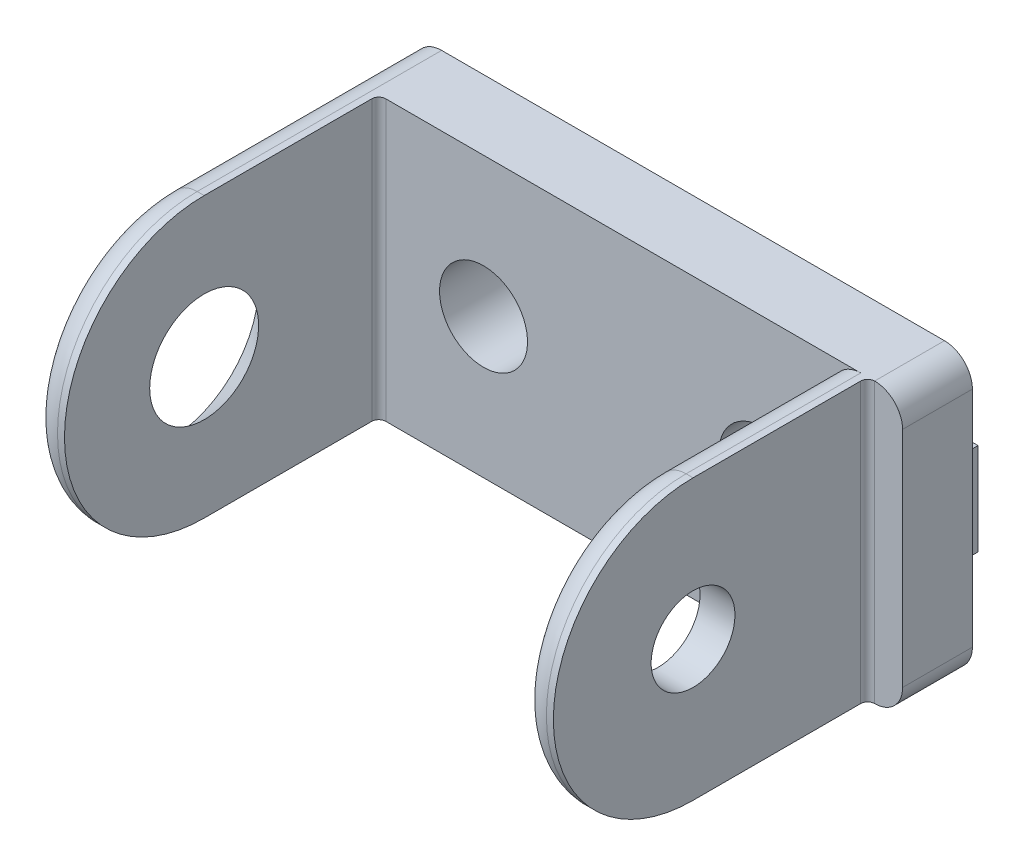
SolidWorks part; units mm, degrees
ref_plane "前视基准面" through (0, 0, 0) normal (0, 0, 1) x (1, 0, 0)
ref_plane "上视基准面" through (0, 0, 0) normal (0, 1, 0) x (1, 0, 0)
ref_plane "右视基准面" through (0, 0, 0) normal (1, 0, 0) x (0, 0, -1)
other "Configuration Table"
sketch "草图1" plane through (0, 0, 0) normal (0, 0, 1) x (1, 0, 0)
  line L0 (0, 0) -> (40, 0)
  line L1 (40, 0) -> (40, -20)
  line L2 (40, -20) -> (0, -20)
  line L3 (0, -20) -> (0, 0)
extrude "凸台-拉伸1" add sketch "草图1" along normal blind 5
sketch "草图2" plane through (0, 0, 0) normal (0, 0, 1) x (1, 0, 0)
  line L0 (0, 0) -> (2.5, 0)
  line L1 (2.5, 0) -> (2.5, -20)
  line L2 (0, -20) -> (40, -20) construction
  line L3 (2.5, -20) -> (0, -20)
  line L4 (0, -20) -> (0, 0)
  line L5 (0, 0) -> (0, -20)
extrude "凸台-拉伸2" add sketch "草图2" along normal blind 27.5 contours L4 L3 L1 L0 region at (1.25, -10, 0)
sketch "草图3" plane through (0, 0, 0) normal (0, 0, -1) x (-1, 0, 0)
  line L0 (0, -10) -> (-35.75, -10)
  line L1 (0, 0) -> (0, -20) construction
  line L2 (-40, -20) -> (-40, 0) construction
  line L3 (-35.75, -6.7) -> (-35.75, -13.3)
  line L4 (-35.75, -6.7) -> (-39, -6.7)
  line L5 (-39, -6.7) -> (-39, -13.3)
  line L6 (-39, -13.3) -> (-35.75, -13.3)
  line L7 (-39, -10) -> (-40, -10)
  line L20 (-33.3, -1) -> (-33.3, -4.25)
  line L21 (-26.7, -4.25) -> (-33.3, -4.25)
  line L22 (-26.7, -4.25) -> (-26.7, -1)
  line L23 (-26.7, -1) -> (-33.3, -1)
  line L24 (-35.75, -10) -> (-39, -10)
  line L25 (-20, -20) -> (-20, -10)
  line L26 (0, -20) -> (-40, -20) construction
  line L31 (-1, -6.7) -> (-1, -13.3)
  line L32 (-4.25, -6.7) -> (-1, -6.7)
  line L33 (-4.25, -6.7) -> (-4.25, -13.3)
  line L34 (-1, -13.3) -> (-4.25, -13.3)
  line L39 (-26.7, -19) -> (-26.7, -15.75)
  line L40 (-33.3, -15.75) -> (-26.7, -15.75)
  line L41 (-33.3, -15.75) -> (-33.3, -19)
  line L42 (-33.3, -19) -> (-26.7, -19)
  line L43 (-21, -6.7) -> (-24.25, -6.7) [skipped]
  line L44 (-21, -13.3) -> (-21, -6.7) [skipped]
  line L45 (-24.25, -13.3) -> (-21, -13.3) [skipped]
  line L46 (-24.25, -13.3) -> (-24.25, -6.7) [skipped]
  line L47 (-6.7208, -18.9792) -> (-13.3208, -18.9792)
  line L48 (-13.3208, -18.9792) -> (-13.3208, -15.7292)
  line L49 (-6.7208, -15.7292) -> (-13.3208, -15.7292)
  line L50 (-6.7208, -15.7292) -> (-6.7208, -18.9792)
  line L55 (-13.2792, -0.9792) -> (-6.6792, -0.9792)
  line L56 (-6.6792, -0.9792) -> (-6.6792, -4.2292)
  line L57 (-13.2792, -4.2292) -> (-6.6792, -4.2292)
  line L58 (-13.2792, -4.2292) -> (-13.2792, -0.9792)
  line L59 (-19, -13.2583) -> (-19, -6.6583) [skipped]
  line L60 (-19, -6.6583) -> (-15.75, -6.6583) [skipped]
  line L61 (-15.75, -13.2583) -> (-15.75, -6.6583) [skipped]
  line L62 (-15.75, -13.2583) -> (-19, -13.2583) [skipped]
  circle A0 centre (-30, -10) radius 3.15
  circle A1 centre (-10, -10) radius 3.15
  point P12 (-35.75, -10)
  point P32 (-35, -10)
  point P37 (-30, -10)
  point P58 (-10, -9.9792)
  dimension "D1" = 20
  dimension "D2" = 10
  dimension "D3" = 6.3
  dimension "D4" = 6.3
  dimension "D6" = 4
  dimension "D5" = 5.75
  dimension "D7" = 6.6
  dimension "D9" = 3.25
  dimension "D8" = 4
extrude "切除-拉伸1" cut sketch "草图3" against normal blind 3 contours L58 L57 L56 L55 | L22 L23 L20 L21 | L41 L42 L39 L40 | L50 L49 L48 L47 region at (30, -2.625, 0) region at (30, -17.375, 0) region at (10.0208, -17.3542, 0) region at (9.9792, -2.6042, 0)
extrude "切除-拉伸2" cut sketch "草图3<3>" against normal through all contours L0 A0 | L0 A0 | L0 A1 | L0 A1 region at (30, -11.3369, 0) region at (30, -8.6631, 0) region at (10, -11.3369, 0) region at (10, -8.6631, 0)
sketch "草图3<3>" plane through (0, 0, 0) normal (0, 0, -1) x (-1, 0, 0) same geometry as "草图3"
extrude "凸台-拉伸3" add sketch "草图3<4>" along normal blind 1.4 separate body contours L24 L3 L4 L5 | L3 L24 L5 L6 | L32 L33 L0 L31 | L34 L31 L0 L33 region at (2.625, -11.65, 0) region at (2.625, -8.35, 0) region at (37.375, -11.65, 0) region at (37.375, -8.35, 0)
sketch "草图3<4>" plane through (0, 0, 0) normal (0, 0, -1) x (-1, 0, 0) same geometry as "草图3"
sketch "草图4" plane through (0, 0, 5) normal (0, 0, 1) x (1, 0, 0)
  line L0 (37.5, 0) -> (35, 0)
  line L1 (40, 0) -> (2.5, 0) construction
  line L2 (35, 0) -> (35, -20)
  line L3 (2.5, -20) -> (40, -20) construction
  line L4 (35, -20) -> (37.5, -20)
  line L5 (37.5, -20) -> (37.5, 0)
  line L6 (40, -20) -> (40, 0) construction
  dimension "D1" = 2.5
  dimension "D2" = 5
extrude "凸台-拉伸4" add sketch "草图4" along normal blind 22.5
sketch "草图5" plane through (0, 0, 0) normal (-1, 0, 0) x (0, 0, 1)
  line L3 (27.5, 0) -> (0, 0) construction
  line L4 (17.5, 0) -> (27.5, 0)
  line L5 (27.5, 0) -> (27.5, -20)
  line L6 (27.5, -20) -> (17.5, -20)
  arc A0 (17.5, -20) -> (17.5, 0) centre (17.5, -10) ccw
  circle A1 centre (17.5, -10) radius 3.15
  line M5 (0, -20) -> (27.5, -20)
  line M6 (27.5, -20) -> (27.5, 0)
  line M7 (27.5, 0) -> (0, 0)
  dimension "D1" = 10
  dimension "D2" = 10
  dimension "D3" = 10
extrude "切除-拉伸3" cut sketch "草图5" against normal through all contours A0 L5 M7 | A0 M5 M6 region at (0, -17.7663, 25.2663) region at (0, -2.2337, 25.2663)
sketch "草图6" plane through (37.5, 0, 0) normal (1, 0, 0) x (0, 0, -1)
  line L0 (-17.5, 0) -> (-17.5, -20)
  arc A0 (-17.5, 0) -> (-17.5, -20) centre (-17.5, -10) ccw construction
  circle A1 centre (-17.5, -10) radius 1.4319
hole_wizard "M6 螺纹孔1" positions "草图7" profile "草图8" tap size "M6" standard "GB" end condition up to next
sketch "草图7" plane through (37.5, 0, 0) normal (1, 0, 0) x (0, 0, -1)
  point P0 (-17.5, -10)
cosmetic thread "孔螺蚊线2" parameters "D2"=6
sketch "草图8" plane through (37.5, -10, 17.5) normal (0, 1, 0) x (0, 0, -1)
  line L0 (0, 0) -> (0, 2.501)
  line L1 (0, 2.501) -> (3, 2.501)
  line L2 (3, 2.501) -> (3, 0)
  line L5 (3, 0) -> (0, 0)
  line L11 (0, -6.35) -> (0, 107.95) construction
  dimension "通孔螺纹孔钻头直径" = 6
  dimension "通孔螺纹孔钻头深度" = 2.501
hole_wizard "M6 内六角花形半沉头螺钉的锥形沉头孔1" positions "草图11" profile "草图10" countersink size "M6" standard "GB" end condition up to next
sketch "草图11" plane through (0, 0, 0) normal (-1, 0, 0) x (0, 0, 1)
  point P0 (17.5, -10)
sketch "草图10" plane through (0, -10, 17.5) normal (0, 1, 0) x (0, 0, 1)
  line L0 (0, 0) -> (0, 2.501)
  line L1 (0, 2.501) -> (3.3, 2.501)
  line L2 (3.3, 2.501) -> (3.3, 3.1)
  line L3 (3.3, 3.1) -> (6.4, 0)
  line L5 (6.4, 0) -> (0, 0)
  line L6 (-3.3, 3.1) -> (-6.4, 0) construction
  line L11 (0, -6.35) -> (0, 107.95) construction
  dimension "通孔孔直径" = 6.6
  dimension "通孔孔深度" = 2.501
  dimension "近端锥形沉头孔直径" = 12.8
  dimension "近端锥形沉头孔角度" = 90
fillet "圆角2" radius 2 6 edges at (35, 0, 11.25) (35, -20, 11.25) (0, -20, 8.75) (0, 0, 8.75) (35, -10, 27.5) (0, -10, 27.5)
fillet "圆角3" radius 2 2 edges at (40, 0, 2.5) (40, -20, 2.5)
fillet "圆角4" radius 0.5 2 edges at (37.5, -10, 5) (2.5, -10, 5)
